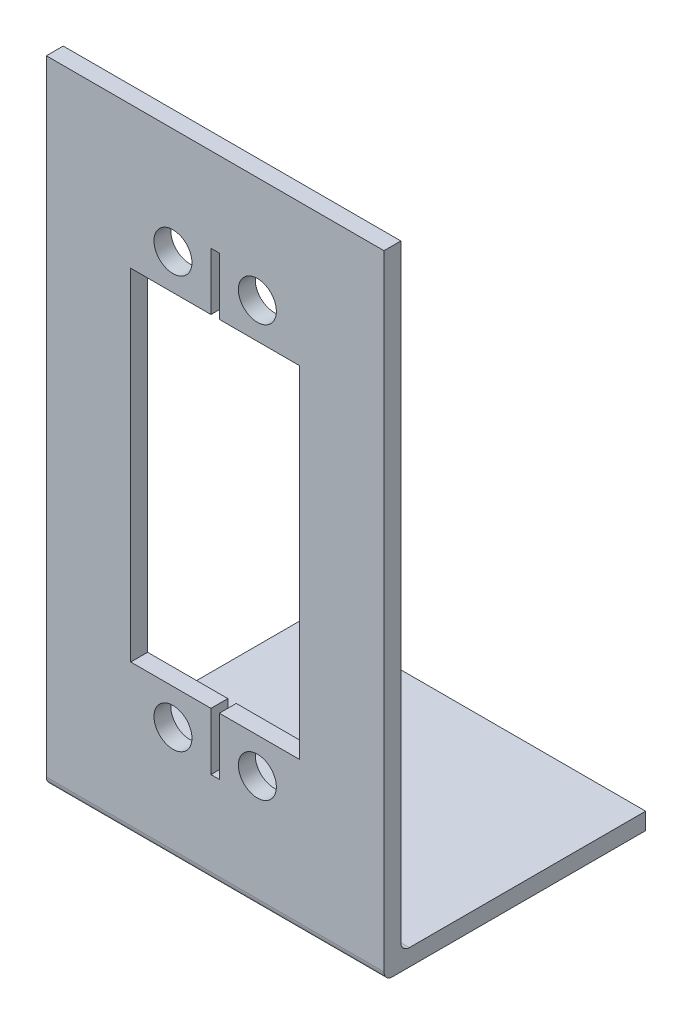
SolidWorks part; units mm, degrees
ref_plane "Front Plane" through (0, 0, 0) normal (0, 0, 1) x (1, 0, 0)
ref_plane "Top Plane" through (0, 0, 0) normal (0, 1, 0) x (1, 0, 0)
ref_plane "Right Plane" through (0, 0, 0) normal (1, 0, 0) x (0, 0, -1)
sketch "Sketch1" plane through (0, 0, 0) normal (0, 1, 0) x (1, 0, 0)
  line L1 (0, 0) -> (40, 0)
  line L2 (0, 0) -> (0, 30)
  line L3 (0, 30) -> (40, 30)
  line L4 (40, 0) -> (40, 30)
  dimension "D1" = 30
  dimension "D2" = 40
extrude "Boss-Extrude1" add sketch "Sketch1" along normal blind 2
sketch "Sketch2" plane through (0, 2, 0) normal (0, 1, 0) x (1, 0, 0)
  line L0 (40, 0) -> (40, 30) construction
  line L1 (0, 0) -> (40, 0)
  line L2 (0, 0) -> (0, 1)
  line L3 (0, 1) -> (40, 1)
  line L4 (40, 0) -> (40, 1)
  line L6 (0, 0) -> (40, 0)
  line L7 (0, 0) -> (0, -1)
  line L8 (0, -1) -> (40, -1)
  line L9 (40, 0) -> (40, -1)
  line M1 (0, 30) -> (0, 0)
  line M2 (0, 0) -> (40, 0)
  line M3 (40, 0) -> (40, 30)
  dimension "D1" = 1
  dimension "D2" = 1
extrude "Boss-Extrude2" add sketch "Sketch2" along normal blind 73 and the other way blind 2 contours L3 M1 M2 M3 | L9 L7 L8 M2 region at (20, 2, -0.5) region at (20, 2, 0.5)
fillet "Fillet1" radius 1 2 edges at (20, 0, 1) (20, 2, -1)
sketch "Sketch4" plane through (0, 0, 1) normal (0, 0, 1) x (1, 0, 0)
  line L0 (20, 75) -> (20, 65)
  line L1 (0, 75) -> (40, 75) construction
  line L3 (20, 65) -> (20.5, 65)
  line L4 (20, 65) -> (20, 58.2)
  line L5 (20, 58.2) -> (20.5, 58.2)
  line L6 (20.5, 65) -> (20.5, 58.2)
  line L7 (20, 65) -> (19.5, 65)
  line L8 (20, 65) -> (20, 58.2)
  line L9 (20, 58.2) -> (19.5, 58.2)
  line L10 (19.5, 65) -> (19.5, 58.2)
  line L11 (20, 58.2) -> (30, 58.2)
  line L12 (20, 58.2) -> (20, 17.8)
  line L13 (20, 17.8) -> (30, 17.8)
  line L14 (30, 58.2) -> (30, 17.8)
  line L15 (20, 58.2) -> (10, 58.2)
  line L16 (20, 58.2) -> (20, 17.8)
  line L17 (20, 17.8) -> (10, 17.8)
  line L18 (10, 58.2) -> (10, 17.8)
  line L19 (20, 17.8) -> (20.5, 17.8)
  line L20 (20, 17.8) -> (20, 11)
  line L21 (20, 11) -> (20.5, 11)
  line L22 (20.5, 17.8) -> (20.5, 11)
  line L23 (20, 17.8) -> (19.5, 17.8)
  line L24 (20, 17.8) -> (20, 11)
  line L25 (20, 11) -> (19.5, 11)
  line L26 (19.5, 17.8) -> (19.5, 11)
  circle A0 centre (15, 62.4) radius 2.25
  circle A1 centre (25, 62.4) radius 2.25
  circle A2 centre (25, 13.6) radius 2.25
  circle A3 centre (15, 13.6) radius 2.25
  dimension "D8" = 4.5
  dimension "D9" = 4.2
  dimension "D10" = 4.5
  dimension "D11" = 4.2
  dimension "D15" = 4.2
  dimension "D1" = 10
  dimension "D2" = 0.5
  dimension "D3" = 0.5
  dimension "D4" = 6.8
  dimension "D5" = 40.4
  dimension "D6" = 10
  dimension "D7" = 10
  dimension "D12" = 0.5
  dimension "D13" = 0.5
  dimension "D14" = 6.8
  dimension "D16" = 4.5
  dimension "D17" = 4.5
  dimension "D18" = 4.2
extrude "Cut-Extrude1" cut sketch "Sketch4" against normal blind 49 contours A0 | L7 L10 L9 L4 | L6 L3 L4 L5 | A1 | L14 L11 L5 L12 L13 | L15 L18 L17 L12 L9 | L17 L26 L25 L20 | A3 | L22 L13 L20 L21 | A2 region at (20.25, 61.6, 1) region at (19.75, 61.6, 1) region at (15, 38, 1) region at (25, 38, 1) region at (19.75, 14.4, 1) region at (20.25, 14.4, 1) region at (15, 62.4, 1) region at (25, 62.4, 1) region at (25, 13.6, 1) region at (15, 13.6, 1)
sketch "Sketch5" plane through (0, 2, 0) normal (0, 1, 0) x (1, 0, 0)
  line L0 (40, 2) -> (40, 30) construction
  line L1 (40, 30) -> (0, 30) construction
  circle A0 centre (20, 15) radius 1.5
  dimension "D1" = 20
  dimension "D2" = 15
hole_wizard "M3 Tapped Hole1" positions "Sketch6" profile "Sketch7" tap size "M3" standard "ISO" end condition through all
sketch "Sketch6" plane through (0, 2, 0) normal (0, 1, 0) x (1, 0, 0)
  point P0 (20, 15)
sketch "Sketch7" plane through (20, 2, -15) normal (1, 0, 0) x (0, 0, 1)
  line L0 (0, 0) -> (0, 2)
  line L1 (0, 2) -> (1.25, 2)
  line L2 (1.25, 2) -> (1.25, 0.275)
  line L3 (1.25, 0.275) -> (1.525, 0)
  line L5 (1.525, 0) -> (0, 0)
  line L6 (-1.25, 0.275) -> (-1.525, 0) construction
  line L11 (0, -6.35) -> (0, 107.95) construction
  dimension "Thru Tap Drill Dia." = 2.5
  dimension "Thru Tap Drill Depth" = 2
  dimension "Near C'Sink Dia." = 3.05
  dimension "Near C'Sink Angle" = 90
cosmetic thread "Hole Thread1" parameters "D2"=3
